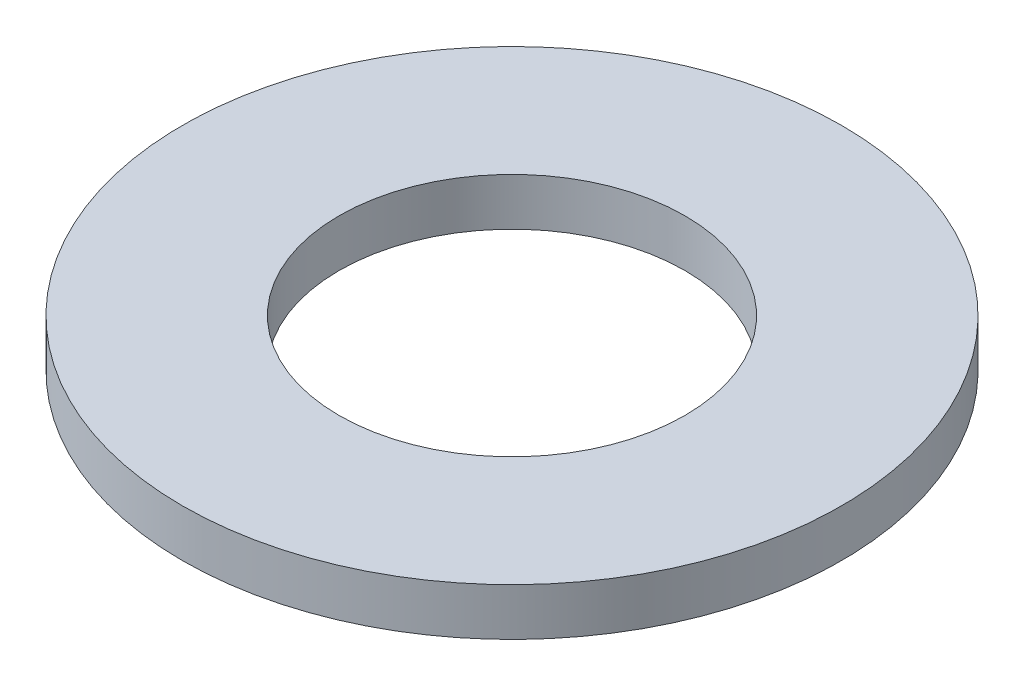
SolidWorks part; units mm, degrees
ref_plane "Front" through (0, 0, 0) normal (0, 0, 1) x (1, 0, 0)
ref_plane "Top" through (0, 0, 0) normal (0, 1, 0) x (1, 0, 0)
ref_plane "Right" through (0, 0, 0) normal (1, 0, 0) x (0, 0, -1)
ref_plane "Plane1" through (0, 0, 0) normal (0, 0, -1) x (-1, 0, 0)
sketch "Sketch1" plane through (0, 0, 0) normal (0, 0, -1) x (-1, 0, 0)
  line L0 (-8.3312, 2.286) -> (-15.875, 2.286)
  line L1 (-15.875, 2.286) -> (-15.875, 0)
  line L2 (-15.875, 0) -> (-8.3312, 0)
  line L3 (-8.3312, 0) -> (-8.3312, 2.286)
  line L4 (0, 0) -> (0, 2.286) construction
revolve "Revolve1" add sketch "Sketch1" angle 360 about L4 reverse direction yes
